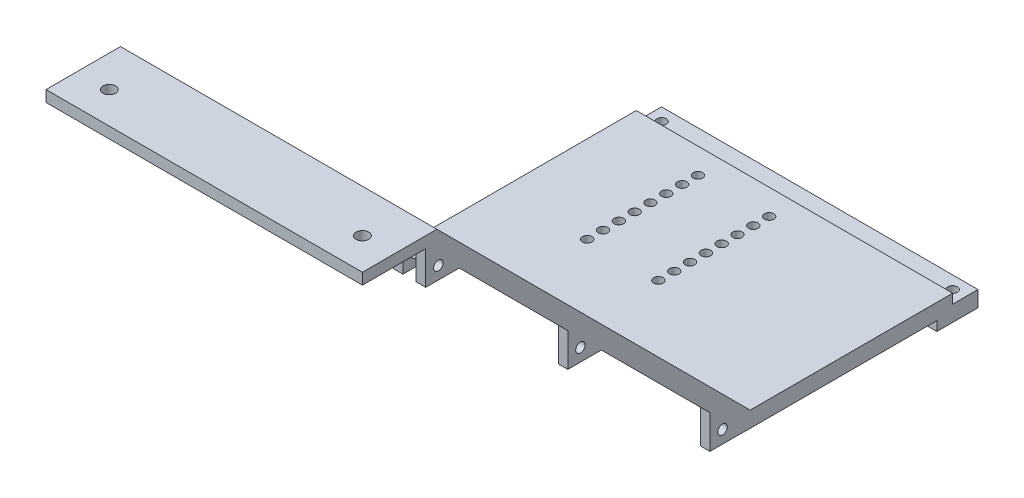
SolidWorks part; units mm, degrees
ref_plane "Front Plane" through (0, 0, 0) normal (0, 0, 1) x (1, 0, 0)
ref_plane "Top Plane" through (0, 0, 0) normal (0, 1, 0) x (1, 0, 0)
ref_plane "Right Plane" through (0, 0, 0) normal (1, 0, 0) x (0, 0, -1)
sketch "Sketch4" plane through (0, 0, 0) normal (1, 0, 0) x (0, 0, -1)
  line L0 (0, 0) -> (-8, 0)
  line L1 (-8, 0) -> (-8, 3)
  line L2 (-8, 3) -> (-72, 3)
  line L3 (-72, 3) -> (-170.9949, 101.9949)
  dimension "D1" = 8
  dimension "D2" = 3
  dimension "D3" = 64
  dimension "D4" = 135
  dimension "D5" = 140
extrude "Extrude-Thin2" add sketch "Sketch4" along normal blind 100 thin thin type one direction reverse wall 5
sketch "Sketch5" plane through (0, 3, 0) normal (0, 1, 0) x (1, 0, 0)
  line L1 (100, -8) -> (100, -72) construction
  line L2 (100, -8) -> (0, -8) construction
  circle A0 centre (50, -16) radius 1.5
  dimension "D2" = 3
  dimension "D1" = 50
  dimension "D3" = 8
extrude "Cut-Extrude1" cut sketch "Sketch5" against normal up to next
pattern_linear "LPattern1" count 8 spacing 5 along (0, 0, 1) count 2 spacing 22.5 along (-1, 0, 0) of "Cut-Extrude1"
sketch "Sketch7" plane through (100, 0, 0) normal (1, 0, 0) x (0, 0, -1)
  line L0 (-170.9949, 101.9949) -> (-174.5305, 101.9949)
  line L1 (-174.5305, 101.9949) -> (-174.5305, 98.4594)
  line L2 (-174.5305, 98.4594) -> (-170.9949, 101.9949)
extrude "Boss-Extrude1" add sketch "Sketch7" against normal up to surface (100 mm away) up to face at (0, 19.2454, 53.3597)
sketch "Sketch8" plane through (0, 0, 174.5305) normal (0, 0, 1) x (1, 0, 0)
  line L1 (0, 101.9949) -> (100, 101.9949)
  line L2 (0, 101.9949) -> (0, 98.4594)
  line L3 (0, 98.4594) -> (100, 98.4594)
  line L4 (100, 101.9949) -> (100, 98.4594)
extrude "Boss-Extrude2" add sketch "Sketch8" along normal blind 20
sketch "Sketch9" plane through (0, 101.9949, 0) normal (0, 1, 0) x (1, 0, 0)
  line L0 (100, -170.9949) -> (100, -194.5305) construction
  line L1 (100, -194.5305) -> (0, -194.5305) construction
  line L2 (0, -170.9949) -> (0, -194.5305) construction
  circle A0 centre (90, -184.5305) radius 2
  circle A1 centre (10, -184.5305) radius 2
  dimension "D1" = 4
  dimension "D2" = 4
  dimension "D3" = 10
  dimension "D4" = 10
  dimension "D5" = 10
  dimension "D6" = 10
extrude "Cut-Extrude2" cut sketch "Sketch9" against normal up to next
sketch "Sketch10" plane through (0, 0, 0) normal (0, 1, 0) x (1, 0, 0)
  line L0 (100, 0) -> (0, 0) construction
  line L1 (100, 0) -> (100, -8) construction
  line L2 (0, 0) -> (0, -8) construction
  circle A0 centre (4, -4) radius 1.5
  circle A1 centre (96, -4) radius 1.5
  dimension "D1" = 3
  dimension "D2" = 3
  dimension "D3" = 4
  dimension "D4" = 4
  dimension "D5" = 4
extrude "Cut-Extrude3" cut sketch "Sketch10" against normal up to next
sketch "Sketch11" plane through (100, 0, 0) normal (1, 0, 0) x (0, 0, -1)
  line L0 (-174.5305, 98.4594) -> (-174.5305, 87.8528)
  line L1 (-174.5305, 87.8528) -> (-163.9239, 87.8528)
  line L2 (-74.0711, -2) -> (-174.5305, 98.4594) construction
  line L3 (-174.5305, 98.4594) -> (-163.9239, 87.8528)
  dimension "D1" = 15
extrude "Boss-Extrude3" add sketch "Sketch11" against normal blind 3
sketch "Sketch12" plane through (100, 0, 0) normal (1, 0, 0) x (0, 0, -1)
  line L0 (-174.5305, 98.4594) -> (-174.5305, 87.8528) construction
  line L1 (-174.5305, 87.8528) -> (-163.9239, 87.8528) construction
  circle A0 centre (-170.5305, 91.8528) radius 1.5
  dimension "D1" = 3
  dimension "D2" = 4
  dimension "D3" = 4
extrude "Cut-Extrude4" cut sketch "Sketch12" against normal up to next
pattern_linear "LPattern2" count 3 spacing 63.5 along (0, -0.7071, -0.7071) count 2 spacing 97 along (-1, 0, 0) of "Boss-Extrude3", "Cut-Extrude4"
sketch "Sketch13" plane through (0, -2, 0) normal (0, -1, 0) x (1, 0, 0)
  line L0 (0, 13) -> (0, 74.0711) construction
  line L1 (0, 48.535) -> (3, 48.535)
  line L2 (0, 48.535) -> (0, 38.535)
  line L3 (0, 38.535) -> (3, 38.535)
  line L4 (3, 48.535) -> (3, 38.535)
  dimension "D1" = 3
  dimension "D2" = 10
  dimension "D3" = 25.535
extrude "Boss-Extrude4" add sketch "Sketch13" along normal blind 10
sketch "Sketch14" plane through (0, 0, 0) normal (-1, 0, 0) x (0, 0, 1)
  line L0 (38.535, -12) -> (38.535, -2) construction
  line L1 (48.535, -12) -> (38.535, -12) construction
  circle A0 centre (43.535, -7) radius 1.5
  dimension "D1" = 3
  dimension "D2" = 5
  dimension "D3" = 5
extrude "Cut-Extrude5" cut sketch "Sketch14" against normal up to next
sketch "Sketch15" plane through (0, -34.5, 34.5) normal (0, 0.7071, -0.7071) x (1, 0, 0)
  line L0 (100, -53.033) -> (100, -193.033) construction
  line L1 (100, -193.033) -> (0, -193.033) construction
  circle A0 centre (84, -176.233) radius 3.4
  circle A1 centre (84, -161.233) radius 3.4
  circle A2 centre (84, -146.233) radius 3.4
  circle A5 centre (84, -131.233) radius 3.4
  circle A6 centre (84, -116.233) radius 3.4
  circle A7 centre (84, -101.233) radius 3.4
  circle A8 centre (84, -86.233) radius 3.4
  dimension "D1" = 6.8
  dimension "D2" = 6.8
  dimension "D3" = 6.8
  dimension "D8" = 6.8
  dimension "D9" = 6.8
  dimension "D10" = 6.8
  dimension "D11" = 6.8
  dimension "D4" = 16
  dimension "D5" = 16.8
  dimension "D6" = 15
  dimension "D7" = 15
  dimension "D12" = 15
  dimension "D13" = 15
  dimension "D14" = 15
  dimension "D15" = 15
extrude "Cut-Extrude6" cut sketch "Sketch15" against normal up to next
sketch "Sketch16" plane through (0, -34.5, 34.5) normal (0, 0.7071, -0.7071) x (1, 0, 0)
  circle A0 centre (59, -161.233) radius 3.4
  circle A1 centre (44, -161.233) radius 3.4
  circle A2 centre (29, -161.233) radius 3.4
  circle A3 centre (14, -161.233) radius 3.4
  circle A5 centre (84, -161.233) radius 3.4 construction
  circle A6 centre (66.5, -146.233) radius 3.4
  circle A7 centre (51.5, -146.233) radius 3.4
  circle A8 centre (36.5, -146.233) radius 3.4
  circle A9 centre (21.5, -146.233) radius 3.4
  circle A10 centre (6.5, -146.233) radius 3.4
  circle A12 centre (51.5, -131.233) radius 3.4
  circle A13 centre (36.5, -131.233) radius 3.4
  circle A14 centre (21.5, -131.233) radius 3.4
  point P26 (0, 0)
  point P27 (0, 0)
  dimension "D1" = 6.8
  dimension "D2" = 15
  dimension "D3" = 15
  dimension "D7" = 6.8
  dimension "D14" = 6.8
  dimension "D4" = 15
  dimension "D5" = 0
  dimension "D6" = 25
  dimension "D8" = 15
  dimension "D9" = 15
  dimension "D10" = 15
  dimension "D11" = 15
  dimension "D12" = 7.5
  dimension "D13" = 15
  dimension "D15" = 15
  dimension "D16" = 15
  dimension "D17" = 15
extrude "Cut-Extrude7" cut sketch "Sketch16" against normal up to next
sketch "Sketch17" plane through (0, -34.5, 34.5) normal (0, 0.7071, -0.7071) x (1, 0, 0)
  circle A0 centre (51.5, -111.233) radius 3.4
  circle A1 centre (36.5, -106.233) radius 3.4
  circle A2 centre (21.5, -111.233) radius 3.4
  circle A3 centre (36.5, -131.233) radius 3.4 construction
  circle A4 centre (84, -116.233) radius 3.4 construction
  point P6 (45.2954, -102.9177)
  point P7 (0, 0)
  point P8 (54.2472, -116.3215)
  point P9 (0, 0)
  point P12 (0, 0)
  point P15 (51.5, -111.9239)
  dimension "D1" = 6.8
  dimension "D4" = 5
  dimension "D2" = 15
  dimension "D3" = 15
  dimension "D5" = 0
  dimension "D6" = 5
extrude "Cut-Extrude8" cut sketch "Sketch17" against normal up to next
pattern_linear "LPattern3" count 4 spacing 15 along (0, -0.7071, -0.7071) of "Cut-Extrude8"
